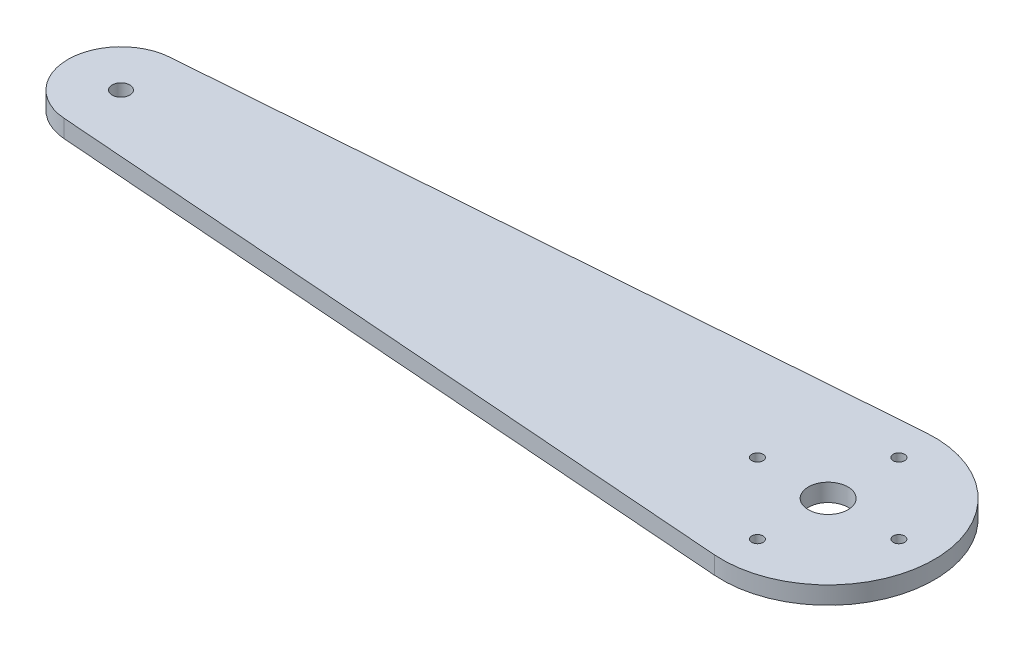
SolidWorks part; units mm, degrees
ref_plane "Front Plane" through (0, 0, 0) normal (0, 0, 1) x (1, 0, 0)
ref_plane "Top Plane" through (0, 0, 0) normal (0, 1, 0) x (1, 0, 0)
ref_plane "Right Plane" through (0, 0, 0) normal (1, 0, 0) x (0, 0, -1)
sketch "Sketch1" plane through (0, 0, 0) normal (0, 1, 0) x (1, 0, 0)
  line L0 (-127.7144, 9.4982) -> (-1.4288, 18.9963)
  line L1 (-127.7144, -9.4982) -> (-1.4287, -18.9963)
  line L2 (-111.3601, 0) -> (-50111.3601, 0) construction
  line L3 (0, -984.3615) -> (0, 49015.6385) construction
  line L4 (0, 0) -> (0, 12.7) construction
  line L5 (0, 0) -> (12.7, 0) construction
  arc A0 (-1.4287, -18.9963) -> (-1.4288, 18.9963) centre (0, 0) ccw
  arc A1 (-127.7144, 9.4982) -> (-127.7144, -9.4982) centre (-127, 0) ccw
  circle A2 centre (-127, 0) radius 1.5875
  circle A3 centre (0, 0) radius 3.556
  circle A4 centre (0, 12.7) radius 1.016
  circle A5 centre (12.7, 0) radius 1.016
  circle A6 centre (0, -12.7) radius 1.016
  circle A7 centre (-12.7, 0) radius 1.016
  dimension "D1" = 9.525
  dimension "D2" = 19.05
  dimension "D4" = 3.175
  dimension "D5" = 7.112
  dimension "D6" = 2.032
  dimension "D3" = 127
  dimension "D7" = 12.7
  dimension "D9" = 90
  dimension "D10" = 12.7
  dimension "D8" = 4
extrude "Boss-Extrude1" add sketch "Sketch1" along normal blind 3.175
